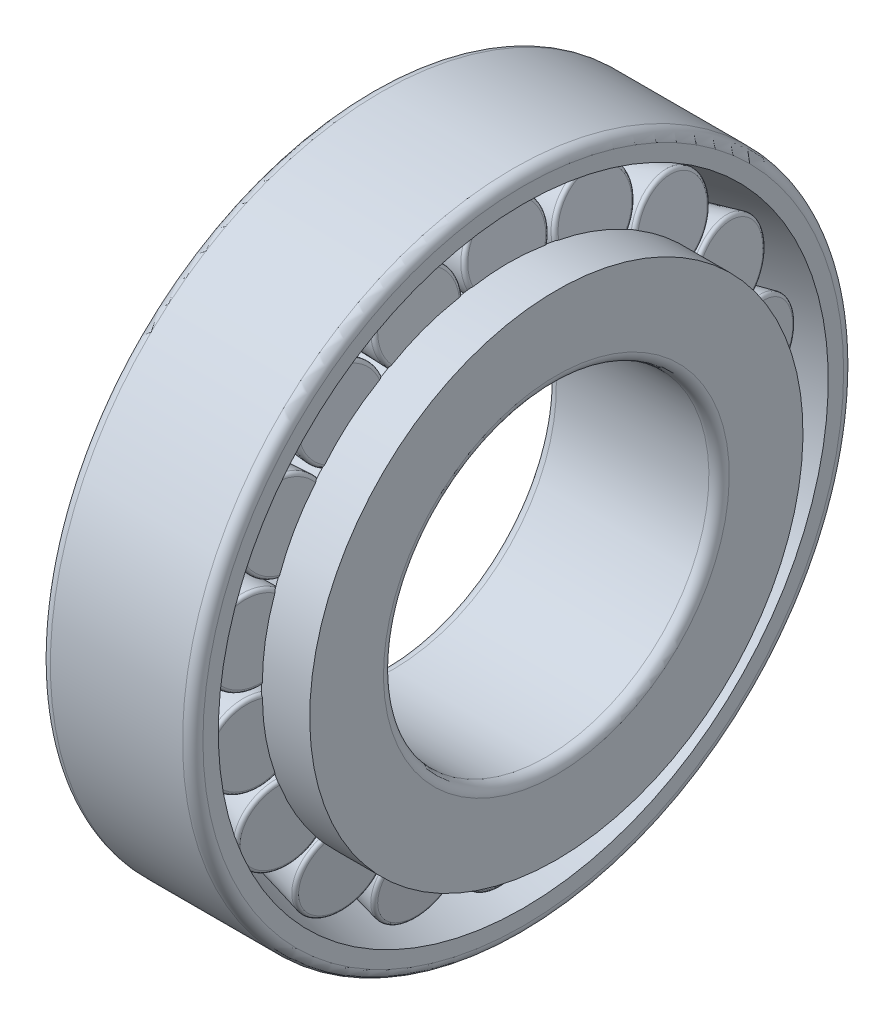
SolidWorks part; units mm, degrees
ref_plane "Front" through (0, 0, 0) normal (0, 0, 1) x (1, 0, 0)
ref_plane "Top" through (0, 0, 0) normal (0, 1, 0) x (1, 0, 0)
ref_plane "Right" through (0, 0, 0) normal (1, 0, 0) x (0, 0, -1)
other "Configuration Table"
sketch "Sketch1" plane through (0, 0, 0) normal (0, 0, 1) x (1, 0, 0)
  line L0 (10.753, 0) -> (13.9916, 0) construction
  line L1 (7.5, 29.9899) -> (7.5, 31.5)
  line L2 (6.5, 32.5) -> (-6.5, 32.5)
  line L3 (-7.5, 31.5) -> (-7.5, 26.25)
  line L4 (-7.5, 26.25) -> (7.5, 29.9899)
  line L5 (-6.247, 17) -> (-6.247, 22.0124)
  line L6 (-5.247, 16) -> (9.753, 16)
  line L7 (10.753, 17) -> (10.753, 24.2704)
  line L8 (-4.3401, 20.5124) -> (-5.3344, 26.79)
  line L9 (6.5, 21.2704) -> (5.2094, 29.4188)
  line L10 (-4.8372, 23.6512) -> (5.8547, 25.3446) construction
  line L11 (-4.3401, 20.5124) -> (6.5, 21.2704)
  line L12 (6.0248, 24.25) -> (10.753, 24.25)
  line L13 (10.753, 24.2704) -> (6.0248, 24.2704)
  line L14 (-6.247, 22.0124) -> (-4.5777, 22.0124)
  arc A0 (-6.5, 32.5) -> (-7.5, 31.5) centre (-6.5, 31.5) ccw
  arc A1 (7.5, 31.5) -> (6.5, 32.5) centre (6.5, 31.5) ccw
  arc A2 (-5.247, 16) -> (-6.247, 17) centre (-5.247, 17) cw
  arc A3 (9.753, 16) -> (10.753, 17) centre (9.753, 17) ccw
  point P19 (-7.5, 32.5)
  point P22 (7.5, 32.5)
  point P24 (0, 32.5)
  point P29 (-6.247, 16)
  point P32 (10.753, 16)
  dimension "D7" = 5
  dimension "D3" = 3
  dimension "D4" = 1.5
revolve "Revolve1" add sketch "Sketch1" angle 360 about L0
sketch "Sketch2" plane through (0, 0, 0) normal (0, 0, 1) x (1, 0, 0)
  line L0 (-4.857, 23.648) -> (9.3992, 25.906) construction
  line L4 (-4.8372, 23.6512) -> (5.8547, 25.3446) construction
  line L5 (-4.857, 23.648) -> (5.8745, 25.3477)
  line L7 (-5.3541, 26.7868) -> (-4.357, 20.4911)
  line L8 (6.5232, 21.252) -> (5.2292, 29.4219)
  line L9 (-4.357, 20.4911) -> (6.5232, 21.252)
  line L10 (-4.857, 23.648) -> (-4.4043, 20.7898)
  line L11 (6.4668, 21.6077) -> (5.8745, 25.3477)
  line L12 (-4.0553, 20.5122) -> (6.1639, 21.2268)
  arc A0 (-4.0553, 20.5122) -> (-4.4043, 20.7898) centre (-4.0783, 20.8414) cw
  arc A1 (6.1639, 21.2268) -> (6.4668, 21.6077) centre (6.1409, 21.556) ccw
revolve "Revolve2" add sketch "Sketch2" angle 360 about L0
sketch "Sketch3" plane through (0, 0, 0) normal (0, 0, 1) x (1, 0, 0)
  line L0 (-7.5, 26.25) -> (7.5, 29.9899) construction
  line L1 (-7.5, 31.5) -> (-7.5, 26.25) construction
  line L2 (6.5, 32.5) -> (-6.5, 32.5) construction
  line L3 (7.5, 29.9899) -> (7.5, 31.5) construction
  line L4 (-7.5, 26.25) -> (7.5, 29.9899)
  line L5 (-7.5, 31.5) -> (-7.5, 26.25)
  line L6 (6.5, 32.5) -> (-6.5, 32.5)
  line L7 (7.5, 29.9899) -> (7.5, 31.5)
  arc A0 (-6.5, 32.5) -> (-7.5, 31.5) centre (-6.5, 31.5) ccw construction
  arc A1 (7.5, 31.5) -> (6.5, 32.5) centre (6.5, 31.5) ccw construction
  arc A2 (-6.5, 32.5) -> (-7.5, 31.5) centre (-6.5, 31.5) ccw
  arc A3 (7.5, 31.5) -> (6.5, 32.5) centre (6.5, 31.5) ccw
revolve "Revolve3" add sketch "Sketch3" angle 360 about axis through (10.753, 0, 0) along (1, 0, 0)
pattern_circular "Circular-Pattern1" count 18 over 360 about axis through (0, 0, 0) along (1, 0, 0) of "Revolve2"
equation "\"gzzj@Sketch1\" =  ( \"DD@Sketch1\" - \"XD@Sketch1\" )  / 4"
equation "\"D1@Sketch1\" = \"DB@Sketch1\" - \"DT@Sketch1\" / 20"
equation "\"D2@Sketch1\" = \"DT@Sketch1\" - \"DC@Sketch1\" + \"XR12@Sketch1\""
equation "\"D4@Sketch1\" = \"D3@Sketch1\" / 2"
equation "\"D2@Sketch2\" = \"gzzj@Sketch1\" / 25"
equation "\"ZJ@Sketch1\" =  ( \"DD@Sketch1\" + \"XD@Sketch1\" )  / 2"
equation "\"D1@Circular-Pattern1\" = int( 3.14159265 / atn(( \"gzzj@Sketch1\" / 2) / sqr( \"ZJ@Sketch1\" * \"ZJ@Sketch1\" /4 - ( \"gzzj@Sketch1\"/ 2) *  ( \"gzzj@Sketch1\"/ 2))))"
